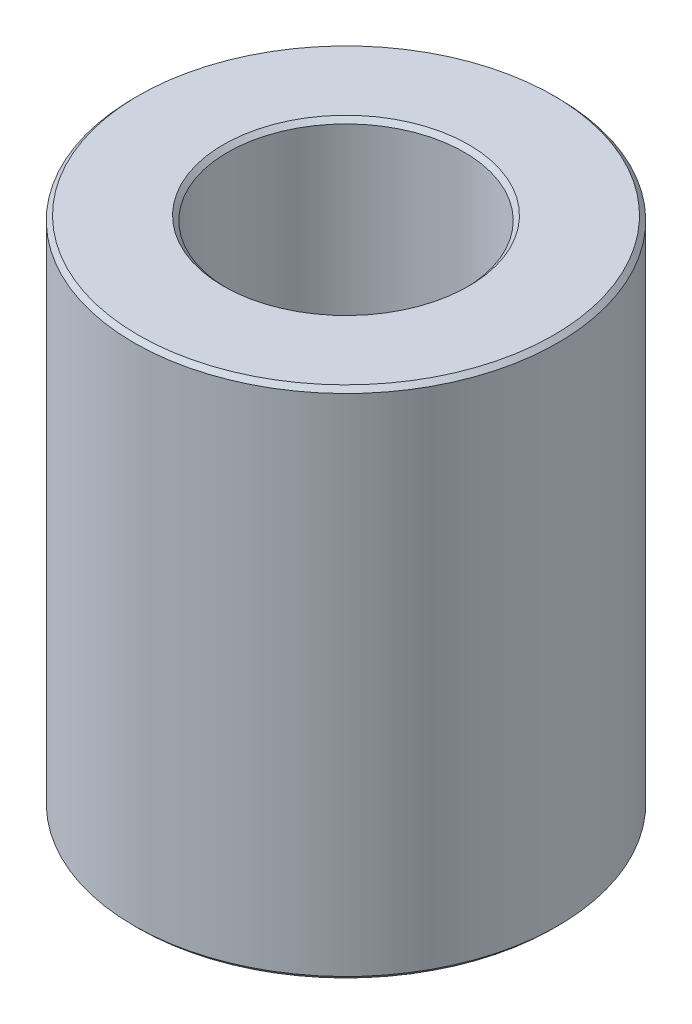
SolidWorks part; units mm, degrees
ref_plane "Front Plane" through (0, 0, 0) normal (0, 0, 1) x (1, 0, 0)
ref_plane "Top Plane" through (0, 0, 0) normal (0, 1, 0) x (1, 0, 0)
ref_plane "Right Plane" through (0, 0, 0) normal (1, 0, 0) x (0, 0, -1)
sketch "Sketch1" plane through (0, 0, 0) normal (0, 1, 0) x (1, 0, 0)
  circle A0 centre (0, 0) radius 40
  dimension "SLEEVE_OD" = 80
extrude "Boss-Extrude1" add sketch "Sketch1" along normal blind 96.9426
sketch "Sketch2" plane through (0, 0, 0) normal (0, 1, 0) x (1, 0, 0)
  circle A0 centre (0, 0) radius 22.3212
  dimension "BORE_D" = 44.6424
extrude "Cut-Extrude1" cut sketch "Sketch2" along normal through all
chamfer "Chamfer1" distance 0.8295 angle 45 4 edges at (0, 96.9426, 22.3212) (0, 0, 22.3212) (0, 0, 40) (0, 96.9426, 40)
